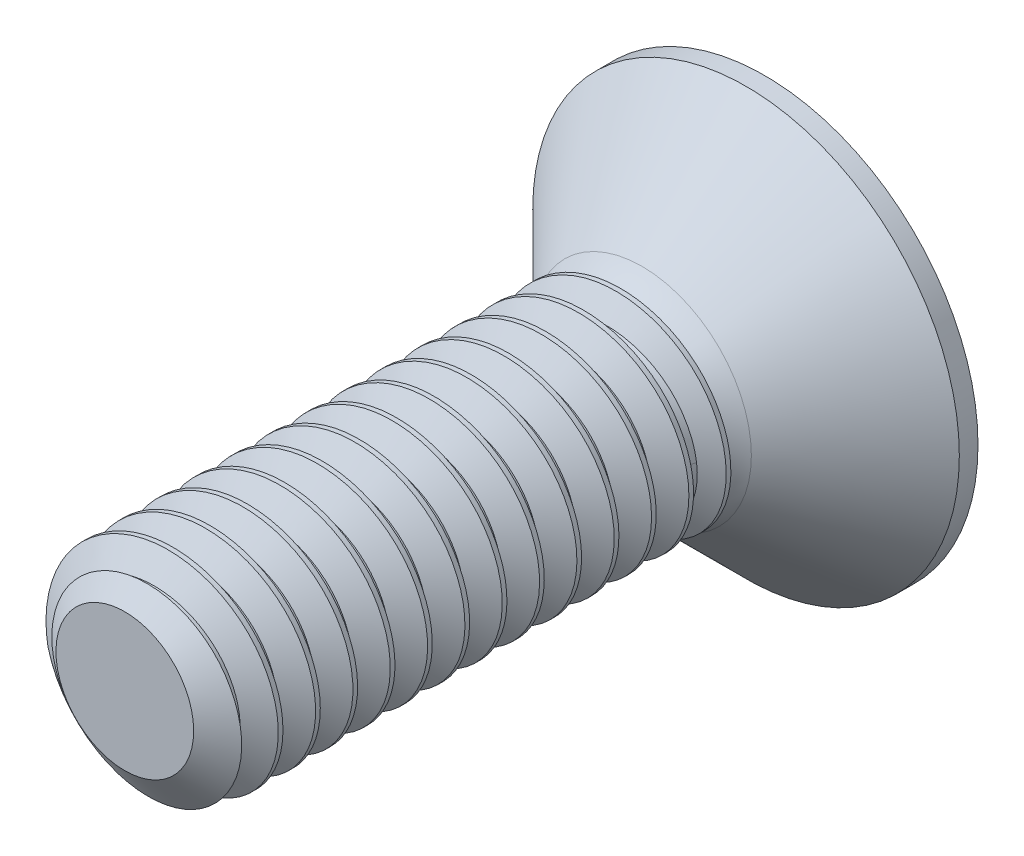
SolidWorks part; units mm, degrees
ref_plane "Front Plane" through (0, 0, 0) normal (0, 0, 1) x (1, 0, 0)
ref_plane "Top Plane" through (0, 0, 0) normal (0, 1, 0) x (1, 0, 0)
ref_plane "Right Plane" through (0, 0, 0) normal (1, 0, 0) x (0, 0, -1)
sketch "Sketch1" plane through (0, 0, 0) normal (0, 0, 1) x (1, 0, 0)
  circle A0 centre (0, 0) radius 2
  dimension "OD" = 4
extrude "Extrude1" add sketch "Sketch1" against normal blind 12
sketch "Sketch2" plane through (0, 0, 0) normal (0, 0, 1) x (1, 0, 0)
  circle A0 centre (0, 0) radius 2 construction
  circle A1 centre (0, 0) radius 2
curve "Helix/Spiral1" pitch 0.7 height 12.7 radius 2 centre (0, 0, 0) axis (0, 0, -1) start towards (0, 1, 0) parameters "pitch"=0.7
sketch "Sketch3" plane through (0, 0, 0) normal (1, 0, 0) x (0, 0, -1)
  line L0 (-0.6125, 2) -> (-0.35, 1.5453)
  line L1 (-0.35, 1.5453) -> (-0.2625, 1.5453)
  line L2 (-0.2625, 1.5453) -> (0, 2)
  line L3 (-0.6125, 2) -> (0, 2)
  line L4 (-0.3063, 2) -> (-0.3063, 1.5453) construction
  line L5 (-0.4813, 1.7727) -> (-0.1313, 1.7727) construction
  line L6 (0, 2) -> (0, -2) construction
  dimension "D1" = 0.0875
  dimension "D2" = 0.35
  dimension "D3" = 60
sweep "Cut-Sweep1" cut profiles "Sketch3" path "Helix/Spiral1"
sketch "Sketch4" plane through (0, 0, 0) normal (1, 0, 0) x (0, 0, -1)
  line L0 (0.4962, 2) -> (0, 1.2913)
  line L1 (0, 1.2913) -> (0, 2)
  line L2 (0.4962, 2) -> (0, 2)
  line L3 (-0.6125, 2) -> (0, 2) construction
  line L4 (0, 0) -> (7.0209, 0) construction
  dimension "D1" = 55
  dimension "D2" = 0.254
revolve "Cut-Revolve1" cut sketch "Sketch4" angle 360 about L4
sketch "Sketch5" plane through (0, 0, 0) normal (1, 0, 0) x (0, 0, -1)
  line L0 (12, -0.9741) -> (12, 1.9864) construction
  line L1 (12, 2.05) -> (18.1906, 2.05)
  line L2 (12, 2.05) -> (12, 0)
  line L3 (12, 0) -> (18, 0)
  line L4 (18, 1.7198) -> (18, 0)
  line L5 (18.1906, 2.05) -> (18, 1.7198)
  line L6 (0, 0) -> (9.9695, 0) construction
  point P3 (18, 2.05)
  point P10 (18, 2.05)
  dimension "D1" = 0.3302
  dimension "Thread min" = 18
  dimension "D2" = 0.05
  dimension "D3" = 30
revolve "partially thread" [suppressed] add sketch "Sketch5" angle 360 about L6
sketch "Sketch6" plane through (0, 0, -12) normal (0, 0, -1) x (-1, 0, 0)
  circle A0 centre (0, 0) radius 4
  dimension "head dia" = 8
extrude "Extrude2" add sketch "Sketch6" against normal blind 2.3
sketch "Sketch10" plane through (0, 0, 0) normal (1, 0, 0) x (0, 0, -1)
  line L0 (11.65, -4) -> (9.7, -2.05)
  line L1 (9.7, -2.05) -> (9.7, -4)
  line L2 (11.65, -4) -> (9.7, -4)
  line L3 (0, 0) -> (9.7, 0) construction
  line L4 (9.7, 4) -> (9.7, -4) construction
  line L5 (11.65, 4) -> (9.7, 4) construction
  line L6 (9.7, 2.05) -> (9.7, 4) construction
  line L7 (11.65, 4) -> (9.7, 2.05) construction
  line L8 (9.7, 4) -> (9.7, -4) construction
  line L9 (9.7, 2.05) -> (9.7, -2.05) construction
  dimension "D1" = 45
  dimension "D2" = 0.05
revolve "Cut-Revolve2" cut sketch "Sketch10" angle 360 about L3
sketch "Sketch11" plane through (0, 0, 0) normal (1, 0, 0) x (0, 0, -1)
  line L0 (-0.35, 1.5453) -> (-0.2625, 1.5453) construction
  line L1 (11.65, 4) -> (9.7, 2.05) construction
  line L2 (8.4816, 1.5453) -> (8.4816, 0)
  line L3 (8.4816, 0) -> (9.7, 0)
  line L4 (9.7, 2.05) -> (9.7, 0)
  line L5 (0, 0) -> (9.7, 0) construction
  arc A0 (9.7, 2.05) -> (8.4816, 1.5453) centre (8.4816, 3.2684) cw
revolve "Revolve1" add sketch "Sketch11" angle 360 about L3
sketch "Sketch7" plane through (0, 0, -12) normal (0, 0, 1) x (1, 0, 0)
  line L1 (0, 1.4434) -> (-1.25, 0.7217)
  line L2 (-1.25, 0.7217) -> (-1.25, -0.7217)
  line L3 (-1.25, -0.7217) -> (0, -1.4434)
  line L4 (0, -1.4434) -> (1.25, -0.7217)
  line L5 (1.25, -0.7217) -> (1.25, 0.7217)
  line L6 (1.25, 0.7217) -> (0, 1.4434)
  circle A0 centre (0, 0) radius 1.25 construction
  dimension "hex dia" = 2.5
extrude "Cut-Extrude1" cut sketch "Sketch7" along normal blind 1.875
sketch "Sketch8" plane through (0, 0, -12) normal (0, 0, 1) x (1, 0, 0)
  circle A0 centre (0, 0) radius 1.4434
extrude "Cut-Extrude2" cut sketch "Sketch8" along normal through all draft 45
sketch "Sketch9" plane through (0, 0, 0) normal (1, 0, 0) x (0, 0, -1)
  line L0 (0, 2) -> (0, -2) construction
  line L1 (3.85, 2) -> (3.85, -2) construction
  line L2 (9.7, 2) -> (9.7, -2) construction
  line L3 (9.7, -2.05) -> (9.7, -4) construction
  dimension "D1" = 3.85
equation "\"D3@Helix/Spiral1\" = \"screw length@Extrude1\"+\"pitch@Helix/Spiral1\""
equation "\"D1@Sketch3\" = \"pitch@Helix/Spiral1\"*.125"
equation "\"D2@Sketch3\" = \"pitch@Helix/Spiral1\"*.5"
equation "\"D1@Cut-Extrude1\" = \"hex dia@Sketch7\"*.75"
equation "\"D1@Sketch9\" = \"pitch@Helix/Spiral1\"*5.5"
equation "\"D2@Sketch10\" = \"D2@Sketch5\""
